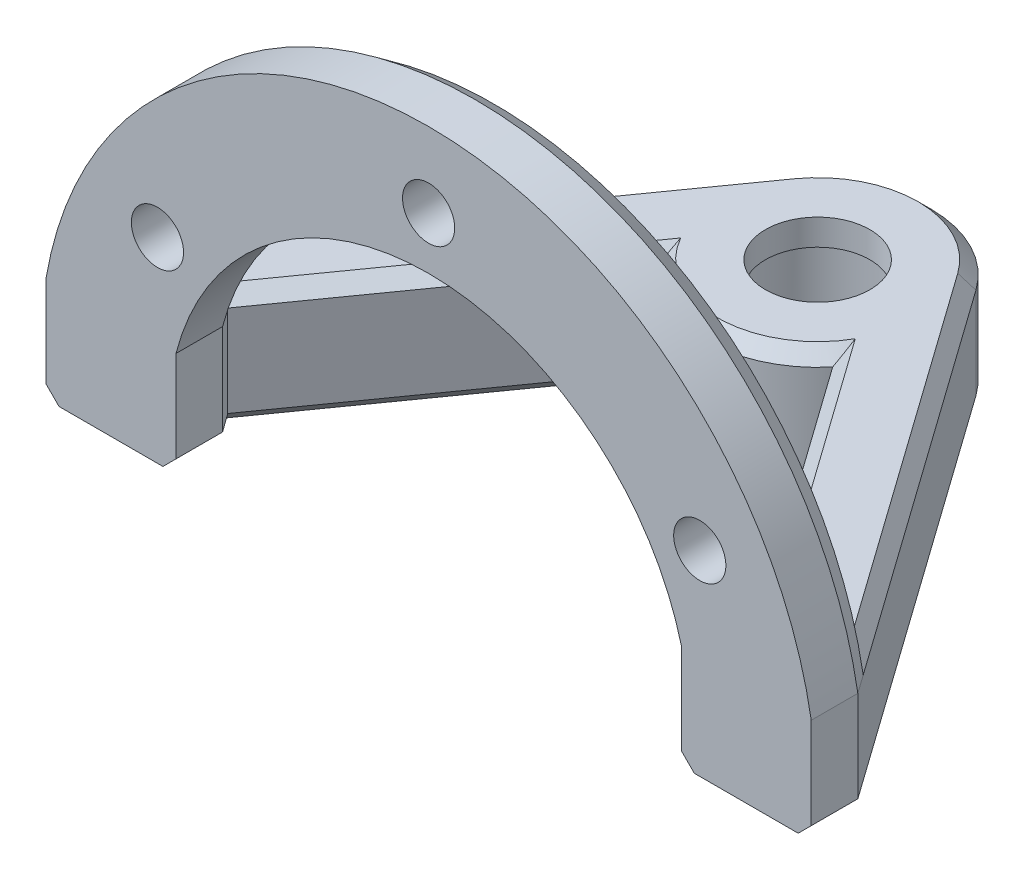
SolidWorks part; units mm, degrees
ref_plane "Front Plane" through (0, 0, 0) normal (0, 0, 1) x (1, 0, 0)
ref_plane "Top Plane" through (0, 0, 0) normal (0, 1, 0) x (1, 0, 0)
ref_plane "Right Plane" through (0, 0, 0) normal (1, 0, 0) x (0, 0, -1)
sketch "Sketch1" plane through (0, 0, 0) normal (0, 0, 1) x (1, 0, 0)
  line L0 (0, 0) -> (0, 24) construction
  line L1 (-29.3268, 5) -> (-19.3649, 5)
  line L2 (19.3649, 5) -> (29.3268, 5)
  circle A3 centre (0, 24) radius 2
  arc A7 (19.3649, 5) -> (-19.3649, 5) centre (0, 0) ccw
  circle A14 centre (0, 0) radius 24 construction
  circle A15 centre (20.7846, 12) radius 2
  circle A19 centre (-20.7846, 12) radius 2
  arc A20 (29.3268, 5) -> (-29.3268, 5) centre (0, 0) ccw
  circle A21 centre (-20.7846, -12) radius 2 [skipped]
  circle A22 centre (0, -24) radius 2 [skipped]
  circle A23 centre (20.7846, -12) radius 2 [skipped]
  point P16 (0, 0)
  dimension "D1" = 48
  dimension "D2" = 40
  dimension "D3" = 4
  dimension "D5" = 59.5
  dimension "D4" = 6
  dimension "D6" = 5
extrude "Boss-Extrude1" add sketch "Sketch1" along normal blind 5
chamfer "Chamfer6" distance 1 angle 55 2 edges at (0, 29.75, 0) (0, 20, 0) first distance on face at (0, 14.9375, 0)
sketch "Sketch4" plane through (0, 5, -5) normal (0, -1, 0) x (-1, 0, 0)
  line L0 (-19.3649, -10) -> (-29.3268, -10) construction
  line L4 (-29.3268, -6.4281) -> (-28.3119, -5) construction
  line L12 (-29.3268, -10) -> (-19.3649, -10)
  line L15 (-29.3268, -6.4281) -> (-29.3268, -10)
  line L16 (0, -2.3789) -> (0, 19.82) construction
  line L17 (-29.3268, -6.4281) -> (-7.0915, 24.8597)
  line L18 (-20.3961, -5) -> (-6.7006, 14.2712)
  line L20 (-29.3268, -10) -> (-29.3268, -6.4281) construction
  line L22 (0, -2.3789) -> (0, 34.8026) construction
  line L23 (0, -10) -> (0, -5) construction
  line L24 (-19.3649, -10) -> (19.3649, -10) construction
  line L25 (20.3961, -5) -> (-20.3961, -5) construction
  line L26 (-19.3649, -10) -> (-19.3649, -6.4281)
  line L27 (-20.3961, -5) -> (-19.3649, -6.4281)
  line L29 (29.3268, -6.4281) -> (28.3119, -5) construction
  line L30 (20.3961, -5) -> (19.3649, -6.4281)
  line L31 (19.3649, -10) -> (19.3649, -6.4281)
  line L32 (20.3961, -5) -> (6.7006, 14.2712)
  line L33 (29.3268, -6.4281) -> (7.0915, 24.8597)
  line L34 (29.3268, -6.4281) -> (29.3268, -10)
  line L35 (29.3268, -10) -> (19.3649, -10)
  circle A0 centre (0, 19.82) radius 5
  arc A1 (-6.7006, 14.2712) -> (6.7006, 14.2712) centre (0, 19.82) ccw
  arc A2 (7.0915, 24.8597) -> (-7.0915, 24.8597) centre (0, 19.82) ccw
  dimension "D1" = 10
  dimension "D3" = 29.82
extrude "Boss-Extrude4" add sketch "Sketch4" along normal blind 8
sketch "Sketch5" plane through (0, 5, 0) normal (0, 1, 0) x (1, 0, 0)
  line L6 (6.7006, 19.2712) -> (20.3961, 0)
  line L7 (20.3961, 0) -> (28.3119, 0)
  line L8 (28.3119, 0) -> (7.0915, 29.8597)
  line L9 (-7.0915, 29.8597) -> (-28.3119, 0)
  line L10 (-28.3119, 0) -> (-20.3961, 0)
  line L11 (-20.3961, 0) -> (-6.7006, 19.2712)
  line L12 (6.7006, 19.2712) -> (20.3961, 0)
  line L13 (20.3961, 0) -> (28.3119, 0)
  line L14 (28.3119, 0) -> (7.0915, 29.8597)
  line L15 (-7.0915, 29.8597) -> (-28.3119, 0)
  line L16 (-28.3119, 0) -> (-20.3961, 0)
  line L17 (-20.3961, 0) -> (-6.7006, 19.2712)
  arc A2 (7.0915, 29.8597) -> (-7.0915, 29.8597) centre (0, 24.82) ccw
  arc A3 (-6.7006, 19.2712) -> (6.7006, 19.2712) centre (0, 24.82) ccw
  arc A4 (7.0915, 29.8597) -> (-7.0915, 29.8597) centre (0, 24.82) ccw
  arc A5 (-6.7006, 19.2712) -> (6.7006, 19.2712) centre (0, 24.82) ccw
  circle A6 centre (0, 24.82) radius 4
  dimension "D2" = 8
  dimension "D1" = 0
extrude "Boss-Extrude5" add sketch "Sketch5" along normal blind 1 and the other way blind 1
chamfer "Chamfer8" distance 1 angle 45 6 edges at (-13.5483, 6, -9.6356) (0, 6, -16.1201) (13.5483, 6, -9.6356) (17.7017, 6, -14.9298) (0, 6, -33.5199) (-17.7017, 6, -14.9298)
chamfer "Chamfer9" distance 1 angle 45 12 edges at (-29.3268, -3, 3.2141) (-18.2091, -3, -14.2158) (0, -3, -33.5199) (18.2091, -3, -14.2158) (29.3268, -3, 3.2141) (-19.3649, -3, 3.2141) (-19.8805, -3, 0.7141) (19.3649, -3, 3.2141) (19.8805, -3, 0.7141) (-13.5483, -3, -9.6356) (0, -3, -16.1201) (13.5483, -3, -9.6356)
